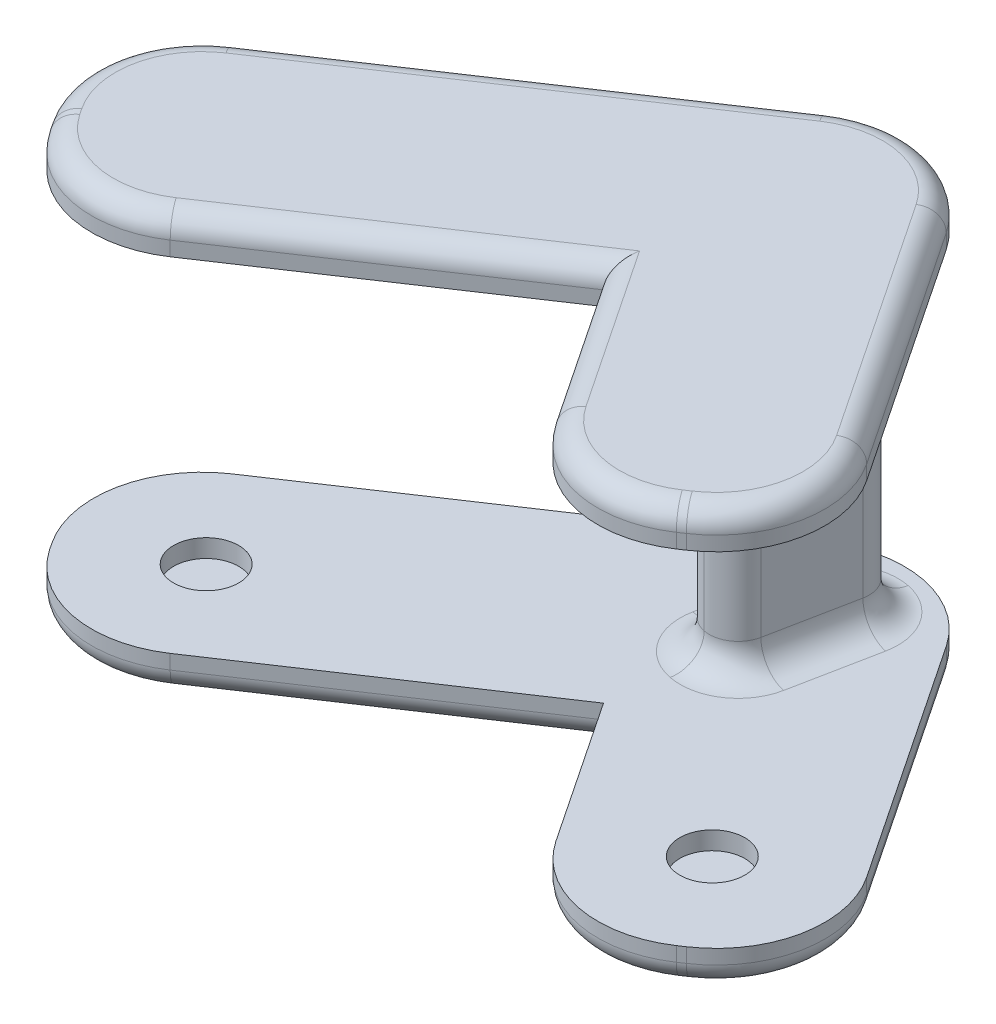
SolidWorks part; units mm, degrees
ref_plane "Alzado" through (0, 0, 0) normal (0, 0, 1) x (1, 0, 0)
ref_plane "Planta" through (0, 0, 0) normal (0, 1, 0) x (1, 0, 0)
ref_plane "Vista lateral" through (0, 0, 0) normal (1, 0, 0) x (0, 0, -1)
sketch "Croquis1" plane through (0, 0, 0) normal (0, 1, 0) x (1, 0, 0)
  line L7 (-12.888, -8.6111) -> (-4.2769, -21.499) construction
  line L11 (-4.2769, -21.499) -> (-21.499, 4.2769)
  line L12 (-4.2769, -21.499) -> (44.1184, 10.8362)
  line L13 (-21.499, 4.2769) -> (40.7235, 45.8507)
  line L15 (52.6722, 53.8342) -> (40.7235, 45.8507)
  line L16 (52.6722, 53.8342) -> (91.499, -4.2769)
  line L17 (44.1184, 10.8362) -> (65.7231, -21.499)
  line L18 (91.499, -4.2769) -> (65.7231, -21.499)
  dimension "D1" = 31
  dimension "D7" = 31
extrude "Saliente-Extruir2" add sketch "Croquis1" along normal blind 5
sketch "Croquis2" plane through (0, 5, 0) normal (0, 1, 0) x (1, 0, 0)
  line L2 (91.499, -4.2769) -> (52.6722, 53.8342) construction
  line L3 (65.7231, -21.499) -> (91.499, -4.2769) construction
  circle A0 centre (0, 0) radius 4.5
  circle A1 centre (70, 0) radius 4.5
  dimension "D1" = 9
  dimension "D2" = 9
  dimension "D3" = 15.5
  dimension "D4" = 15.5
extrude "Cortar-Extruir1" cut sketch "Croquis2" against normal blind 2.5
sketch "Croquis4" plane through (0, 5, 0) normal (0, 1, 0) x (1, 0, 0)
  line L12 (52.6722, 53.8342) -> (44.1184, 10.8362) construction
  line L13 (52.6722, 53.8342) -> (47.9686, 50.6916)
  line L14 (52.6722, 53.8342) -> (-21.499, 4.2769) construction
  line L15 (47.9686, 50.6916) -> (39.4148, 7.6935)
  line L16 (-4.2769, -21.499) -> (44.1184, 10.8362) construction
  line L17 (39.4148, 7.6935) -> (44.1184, 10.8362)
  line L18 (44.1184, 10.8362) -> (47.2611, 6.1326)
  line L19 (44.1184, 10.8362) -> (65.7231, -21.499) construction
  line L20 (47.2611, 6.1326) -> (55.8149, 49.1307)
  line L21 (91.499, -4.2769) -> (52.6722, 53.8342) construction
  line L22 (55.8149, 49.1307) -> (52.6722, 53.8342)
  dimension "D1" = 4
  dimension "D2" = 4
extrude "Saliente-Extruir3" add sketch "Croquis4" along normal blind 47.5
sketch "Croquis5" plane through (0, 52.5, 0) normal (0, 1, 0) x (1, 0, 0)
  line L0 (-21.499, 4.2769) -> (-4.2769, -21.499)
  line L1 (-4.2769, -21.499) -> (44.1184, 10.8362)
  line L2 (44.1184, 10.8362) -> (65.7231, -21.499)
  line L3 (65.7231, -21.499) -> (91.499, -4.2769)
  line L4 (91.499, -4.2769) -> (52.6722, 53.8342)
  line L5 (52.6722, 53.8342) -> (-21.499, 4.2769)
extrude "Saliente-Extruir4" add sketch "Croquis5" along normal blind 5
sketch "Croquis6" plane through (0, 52.5, 0) normal (0, -1, 0) x (1, 0, 0)
  line L0 (-21.499, -4.2769) -> (-4.2769, 21.499) construction
  line L1 (65.7231, 21.499) -> (91.499, 4.2769) construction
  line L2 (47.2611, -6.1326) -> (65.7231, 21.499) construction
  circle A0 centre (0, 0) radius 10.5
  circle A1 centre (70, 0) radius 10.5
  dimension "D1" = 21
  dimension "D2" = 21
  dimension "D3" = 15.5
  dimension "D4" = 15.5
  dimension "D5" = 15.5
extrude "Cortar-Extruir2" cut sketch "Croquis6" against normal blind 2.5
sketch "Croquis7" plane through (36.4421, 0, 7.2496) normal (-0.9808, 0, -0.1951) x (-0.1951, 0, 0.9808)
  line L0 (-59.0765, 5) -> (-15.2359, 5) construction
  line L1 (-77.6533, 52.5) -> (-51.0765, 52.5)
  line L2 (-77.6533, 52.5) -> (-77.6533, 5)
  line L3 (-77.6533, 5) -> (-51.0765, 5)
  line L4 (-51.0765, 52.5) -> (-51.0765, 5)
  line L5 (-59.0765, 52.5) -> (0, 52.5) construction
  line L6 (-31.0765, 52.5) -> (-11.0765, 52.5)
  line L7 (-31.0765, 52.5) -> (-31.0765, 5)
  line L8 (-31.0765, 5) -> (-11.0765, 5)
  line L9 (-11.0765, 52.5) -> (-11.0765, 5)
  line L10 (-59.0765, 5) -> (0, 5) construction
  line L12 (-63.0765, 57.5) -> (-63.0765, 0) construction
  dimension "D1" = 20
  dimension "D2" = 12
  dimension "D3" = 20
extrude "Cortar-Extruir3" cut sketch "Croquis7" against normal blind 12.5
fillet "Redondeo1" radius 15 10 edges at (-4.2769, 2.5, 21.499) (-21.499, 2.5, -4.2769) (52.6722, 55, -53.8342) (91.499, 2.5, 4.2769) (65.7231, 2.5, 21.499) (-21.499, 55, -4.2769) (-4.2769, 55, 21.499) (65.7231, 55, 21.499) (91.499, 55, 4.2769) (52.6722, 2.5, -53.8342)
fillet "Redondeo2" radius 3 22 edges at (50.7541, 0, -0.9047) (15.5866, 0, -29.0556) (26.1569, 0, 1.1648) (-12.888, 0, 8.6111) (72.0856, 0, -24.7787) (78.6111, 0, 12.888) (85.4052, 0, 3.0646) (66.9354, 0, 15.4052) (-3.0646, 0, 15.4052) (-15.4052, 0, -3.0646) (51.4599, 0, -47.7404) (15.5866, 57.5, -29.0556) (72.0856, 57.5, -24.7787) (-12.888, 57.5, 8.6111) (26.1569, 57.5, 1.1648) (78.6111, 57.5, 12.888) (-15.4052, 57.5, -3.0646) (-3.0646, 57.5, 15.4052) (66.9354, 57.5, 15.4052) (85.4052, 57.5, 3.0646) (51.4599, 57.5, -47.7404) (50.7541, 57.5, -0.9047)
fillet "Redondeo3" radius 4 8 edges at (42.5055, 28.75, -23.2297) (44.4566, 5, -33.0375) (46.4077, 28.75, -42.8453) (44.4566, 52.5, -33.0375) (50.3518, 28.75, -21.6688) (52.3029, 52.5, -31.4766) (54.254, 28.75, -41.2844) (52.3029, 5, -31.4766)
